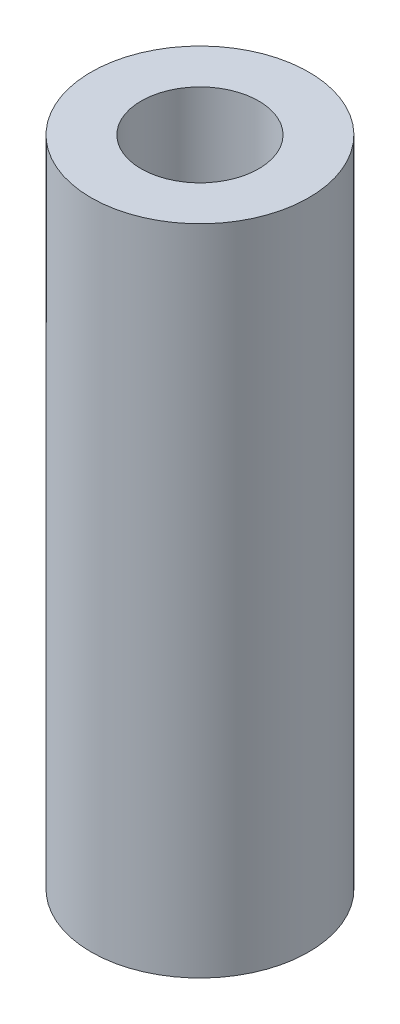
SolidWorks part; units mm, degrees
ref_plane "Front Plane" through (0, 0, 0) normal (0, 0, 1) x (1, 0, 0)
ref_plane "Top Plane" through (0, 0, 0) normal (0, 1, 0) x (1, 0, 0)
ref_plane "Right Plane" through (0, 0, 0) normal (1, 0, 0) x (0, 0, -1)
sketch "Sketch1" plane through (0, 0, 0) normal (0, 1, 0) x (1, 0, 0)
  circle A0 centre (0, 0) radius 5.4
  circle A1 centre (0, 0) radius 10
  dimension "D1" = 10.8
  dimension "D2" = 20
extrude "Boss-Extrude1" add sketch "Sketch1" along normal blind 60
extrude "Boss-Extrude2" add sketch "Sketch1<2>" along normal blind 10 contours A0
sketch "Sketch1<2>" plane through (0, 0, 0) normal (0, 1, 0) x (1, 0, 0) same geometry as "Sketch1"
equation "\"shaftDiam\" = 20mm"
equation "\"keyW\" = 8mm"
equation "\"keyL\" = 10mm"
equation "\"clearance\" = .8mm"
equation "\"handleShaftLen\" = 60mm"
equation "\"panelH\" = 80mm"
equation "\"panelW\" = 110mm"
equation "\"D1@Sketch1\"=\"clearance\"+\"shaftDiam\"/2"
equation "\"D2@Sketch1\"=\"shaftDiam\""
equation "\"D1@Boss-Extrude1\"= \"panelH\" - \"shaftDiam\""
